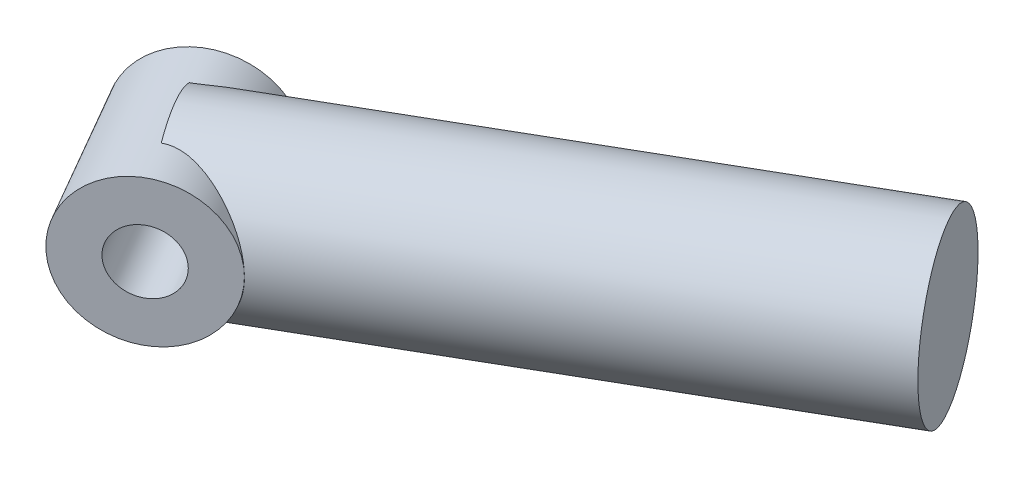
SolidWorks part; units mm, degrees
material "Chrome Stainless Steel"
ref_plane "Front Plane" through (0, 0, 0) normal (0, 0, 1) x (1, 0, 0)
ref_plane "Top Plane" through (0, 0, 0) normal (0, 1, 0) x (1, 0, 0)
ref_plane "Right Plane" through (0, 0, 0) normal (1, 0, 0) x (0, 0, -1)
sketch "Sketch1" plane through (0, 0, 0) normal (0, 1, 0) x (1, 0, 0)
  line L0 (86.6025, 150) -> (0, 0) construction
  line L1 (173.2051, 0) -> (0, 0) construction
  line L2 (86.6025, 150) -> (103.923, 160)
  line L3 (158.0737, 16.2083) -> (93.0737, 128.7917)
  line L4 (181.5544, 35.5385) -> (194.8557, 12.5) construction
  line L5 (173.2051, 0) -> (194.8557, 12.5) construction
  line L6 (86.6025, -150) -> (173.2051, 0) construction
  line L7 (173.2051, 0) -> (159.9038, 23.0385) construction
  line L8 (159.9038, 23.0385) -> (181.5544, 35.5385) construction
  line L9 (181.5544, 35.5385) -> (121.5544, 139.4615) construction
  line L10 (121.5544, 139.4615) -> (99.9038, 126.9615) construction
  line L12 (86.6025, 150) -> (-86.6025, 150) construction
  line L13 (-86.6025, 150) -> (-99.9038, 126.9615) construction
  line L14 (-99.9038, 126.9615) -> (-121.5544, 139.4615) construction
  line L15 (-121.5544, 139.4615) -> (-181.5544, 35.5385) construction
  line L16 (-181.5544, 35.5385) -> (-159.9038, 23.0385) construction
  line L17 (-159.9038, 23.0385) -> (-173.2051, 0) construction
  line L18 (-173.2051, 0) -> (-86.6025, -150) construction
  line L19 (-86.6025, -150) -> (-60, -150) construction
  line L20 (-60, -150) -> (-60, -175) construction
  line L21 (-60, -175) -> (60, -175) construction
  line L22 (60, -175) -> (60, -150) construction
  line L23 (60, -150) -> (86.6025, -150) construction
  line L24 (22.799, 39.489) -> (45.598, 0)
  line L25 (22.799, 39.489) -> (86.6025, 150)
  line L26 (151.5544, 87.5) -> (34.1985, 19.7445) construction
  line L27 (114.7243, 141.2917) -> (103.923, 160)
  line L28 (114.7243, 141.2917) -> (93.0737, 128.7917)
  line L29 (45.598, 0) -> (173.2051, 0)
  line L30 (173.2051, 0) -> (190.5256, 10)
  line L31 (179.7243, 28.7083) -> (190.5256, 10)
  line L32 (179.7243, 28.7083) -> (158.0737, 16.2083)
  line L33 (0, 0) -> (131.7313, -228.1653) construction
  line L34 (140.7291, 81.25) -> (272.4604, -146.9153) construction
  point P4 (101.6025, 168.75)
  point P22 (88.923, 130.7115)
  point P26 (75.6218, 153.75)
  point P34 (125.5737, 72.5)
  dimension "D1" = 162.5
extrude "Boss-Extrude1" add sketch "Sketch1" along normal mid plane 50
ref_plane "Plane1" through (140.7291, 0, -81.25) normal (0.5, 0, 0.866) x (0.866, 0, -0.5)
sketch "Sketch2" plane through (140.7291, 0, -81.25) normal (0.5, 0, 0.866) x (0.866, 0, -0.5)
  line L0 (0, 0) -> (0, -100.0987) construction
  line L1 (12.5, 0) -> (-12.5, 0) construction
  circle A0 centre (0, 0) radius 8
extrude "Cut-Extrude1" cut sketch "Sketch2" against normal mid plane 220
sketch "Sketch3" plane through (140.7291, 0, -81.25) normal (0.5, 0, 0.866) x (0.866, 0, -0.5)
  line L0 (0, 18) -> (-12.5, 18)
  line L1 (-12.5, 25) -> (-12.5, -25) construction
  line L2 (0, -18) -> (-12.5, -18)
  line L3 (-12.5, 18) -> (-12.5, 31.3122)
  line L4 (-12.5, 31.3122) -> (23.9059, 31.3122)
  line L5 (23.9059, 31.3122) -> (23.9059, -29.5052)
  line L6 (-12.5, -29.5052) -> (23.9059, -29.5052)
  line L7 (-12.5, -18) -> (-12.5, -29.5052)
  arc A0 (0, -18) -> (0, 18) centre (0, 0) ccw
extrude "Cut-Extrude2" cut sketch "Sketch3" against normal mid plane 300
ref_plane "Plane2" through (173.2291, 0, -24.9583) normal (0.5, 0, 0.866) x (0.866, 0, -0.5)
sketch "Sketch4" plane through (173.2291, 0, -24.9583) normal (0.5, 0, 0.866) x (0.866, 0, -0.5)
  line L2 (7.5, 16.3631) -> (7.5, 2.7839)
  line L3 (7.5, -2.7839) -> (7.5, -16.3631)
  line L7 (-12.5, 18) -> (0, 18)
  line L8 (-12.5, 31.3122) -> (-12.5, 18)
  line L9 (23.9059, 31.3122) -> (-12.5, 31.3122)
  line L10 (23.9059, -29.5052) -> (23.9059, 31.3122)
  line L11 (-12.5, -29.5052) -> (23.9059, -29.5052)
  line L12 (-12.5, -18) -> (-12.5, -29.5052)
  line L13 (0, -18) -> (-12.5, -18)
  arc A0 (7.5, -2.7839) -> (7.5, 2.7839) centre (0, 0) ccw
  arc A1 (0, -18) -> (0, 18) centre (0, 0) ccw
  arc A2 (7.5, -16.3631) -> (7.5, 16.3631) centre (0, 0) ccw
  dimension "D1" = 0
extrude "Boss-Extrude2" add sketch "Sketch4" along normal blind 21.6025
mirror "Mirror2" about plane through (140.7291, 0, -81.25) normal (0.5, 0, 0.866) of "Boss-Extrude2"
sketch "Sketch5" plane through (34.1985, 0, -19.7445) normal (-0.866, 0, 0.5) x (0.5, 0, 0.866)
  circle A0 centre (0, 0) radius 13
extrude "Cut-Extrude3" cut sketch "Sketch5" against normal blind 50
sketch "Sketch6" plane through (77.4998, 0, -44.7445) normal (-0.866, 0, 0.5) x (0.5, 0, 0.866)
  circle A1 centre (0, 0) radius 13
  circle A2 centre (0, 0) radius 13
  dimension "D1" = 0
extrude "Boss-Extrude3" add sketch "Sketch6" along normal blind 100 separate body
sketch "Sketch7" plane through (140.7291, 0, -81.25) normal (0.5, 0, 0.866) x (0.866, 0, -0.5)
  circle A0 centre (-162.5, 0) radius 5
extrude "Cut-Extrude4" cut sketch "Sketch7" against normal mid plane 100
sketch "Sketch8" plane through (140.7291, 0, -81.25) normal (0.5, 0, 0.866) x (0.866, 0, -0.5)
  circle A0 centre (-162.5, 0) radius 11.5
  circle A1 centre (-162.5, 0) radius 5
extrude "Boss-Extrude4" add sketch "Sketch8" along normal mid plane 26
sketch "Sketch9" plane through (140.7291, 0, -81.25) normal (0.5, 0, 0.866) x (0.866, 0, -0.5)
  line L0 (-162.5, 18.8341) -> (-162.5, 11.5)
  line L1 (-162.5, -11.5) -> (-162.5, -19.8118)
  arc A0 (-162.5, 11.5) -> (-162.5, -11.5) centre (-162.5, 0) ccw
  arc A1 (-162.5, 18.8341) -> (-162.5, -18.8341) centre (-162.5, 0) ccw
extrude "Cut-Extrude5" cut sketch "Sketch9" against normal mid plane 56 contours L0 A1 L1 A0 region at (-0.3647, 15.167, 0.2106)
delete or keep bodies "Body-Delete/Keep 1" type delete bodies bodies 106
ref_plane "Plane3" through (0, 0, 0) normal (0.5, 0, 0.866) x (0.866, 0, -0.5)
ref_axis "Axis1" through (-8.6651, 0, -15.0083) along (0.5, 0, 0.866)
ref_axis "Axis2" through (24.2499, 0, -14.0007) along (0.866, 0, -0.5)
ref_plane "Plane4" through (6.75, 0, 11.6913) normal (0.5, 0, 0.866) x (0.866, 0, -0.5)
sketch "Sketch10" plane through (6.75, 0, 11.6913) normal (0.5, 0, 0.866) x (0.866, 0, -0.5)
  line L0 (0, 11.5) -> (21.6263, 13)
  line L1 (89.489, 13) -> (0, 13) construction
  line L2 (21.6263, 13) -> (21.6263, -13)
  line L3 (0, -11.5) -> (21.6263, -13)
  circle A0 centre (0, 0) radius 5 construction
  circle A1 centre (0, 0) radius 11.5
  arc A2 (0, 11.5) -> (0, -11.5) centre (0, 0) ccw
  circle A3 centre (0, 0) radius 5
  dimension "D1" = 0
extrude "Boss-Extrude5" [suppressed] add sketch "Sketch10" along normal blind 10 separate body
pattern_circular "CirPattern2" [suppressed] count 2 over 360 about axis through (24.2499, 0, -14.0007) along (0.866, 0, -0.5) of bodies 111
sketch "Sketch11" [suppressed] plane through (18.7289, 0, -10.8131) normal (0.866, 0, -0.5) x (-0.5, 0, -0.866)
  line L1 (-23.5, 13) -> (23.5, 13)
  line L2 (-23.5, 13) -> (-23.5, -13)
  line L3 (-23.5, -13) -> (23.5, -13)
  line L4 (23.5, 13) -> (23.5, -13)
extrude "Boss-Extrude6" [suppressed] add sketch "Sketch11" against normal blind 10 separate body
sketch "Sketch12" [suppressed] plane through (18.7289, 0, -10.8131) normal (0.866, 0, -0.5) x (-0.5, 0, -0.866)
  circle A0 centre (0, 0) radius 13 construction
  circle A1 centre (0, 0) radius 13
extrude "Boss-Extrude7" [suppressed] add sketch "Sketch12" along normal blind 67.8628 separate body
combine bodies "Combine2" [suppressed] operation type add bodies to combine 112 113 114 111
delete or keep bodies "Body-Delete/Keep 2" [suppressed] type delete bodies bodies 110
